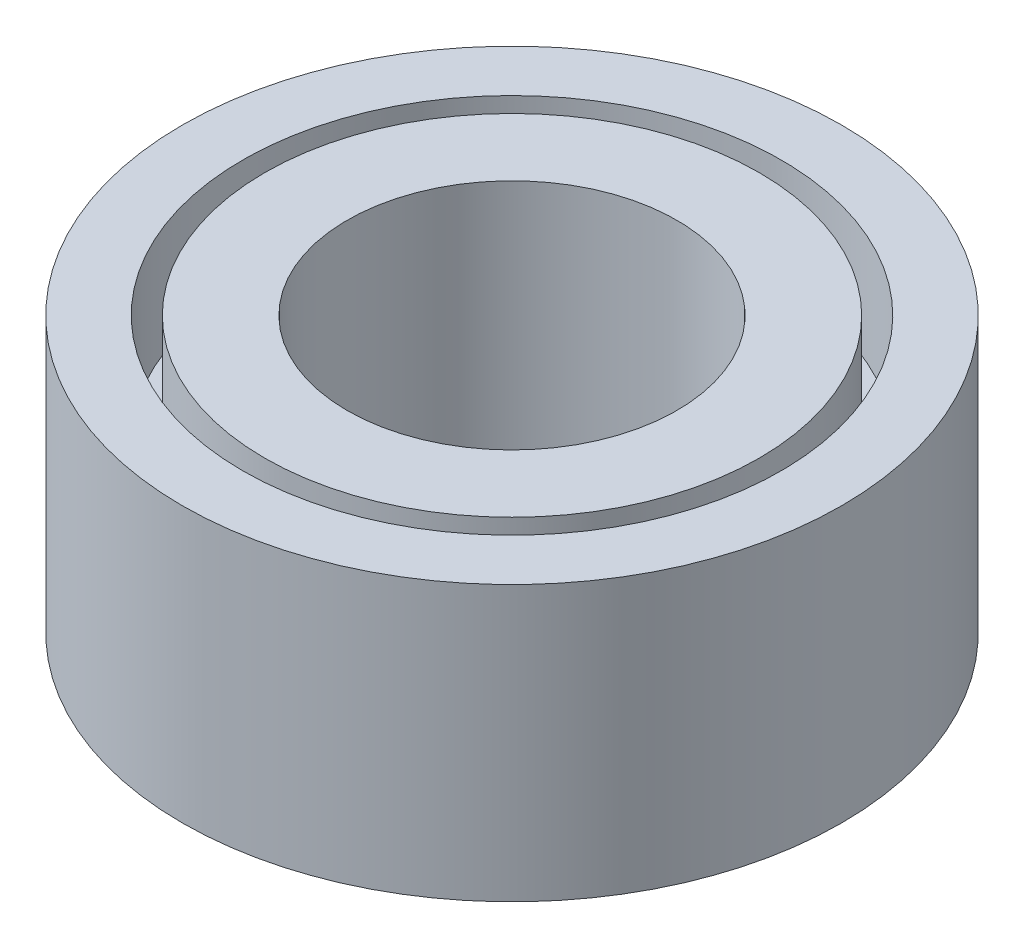
SolidWorks part; units mm, degrees
ref_plane "前视基准面" through (0, 0, 0) normal (0, 0, 1) x (1, 0, 0)
ref_plane "上视基准面" through (0, 0, 0) normal (0, 1, 0) x (1, 0, 0)
ref_plane "右视基准面" through (0, 0, 0) normal (1, 0, 0) x (0, 0, -1)
other "Configuration Table"
sketch "草图1" plane through (0, 0, 0) normal (0, 1, 0) x (1, 0, 0)
  circle A0 centre (0, 0) radius 3
  circle A1 centre (0, 0) radius 1.5
  circle A2 centre (0, 0) radius 2.25
  dimension "D1" = 3
  dimension "D2" = 6
  dimension "D3" = 4.5
extrude "凸台-拉伸1" add sketch "草图1" along normal blind 2.5 contours A1 | A0 region at (0, 0, 0)
extrude "切除-拉伸-薄壁1" cut sketch "草图1<3>" along normal blind 1 thin contours A2 thin type one direction wall 0.2
sketch "草图1<3>" plane through (0, 0, 0) normal (0, 1, 0) x (1, 0, 0) same geometry as "草图1"
extrude "切除-拉伸-薄壁2" cut sketch "草图1<4>" against normal blind 1 from surface thin contours A2 starting at face at (0, 2.5, 3) thin type one direction wall 0.2
sketch "草图1<4>" plane through (0, 0, 0) normal (0, 1, 0) x (1, 0, 0) same geometry as "草图1"
